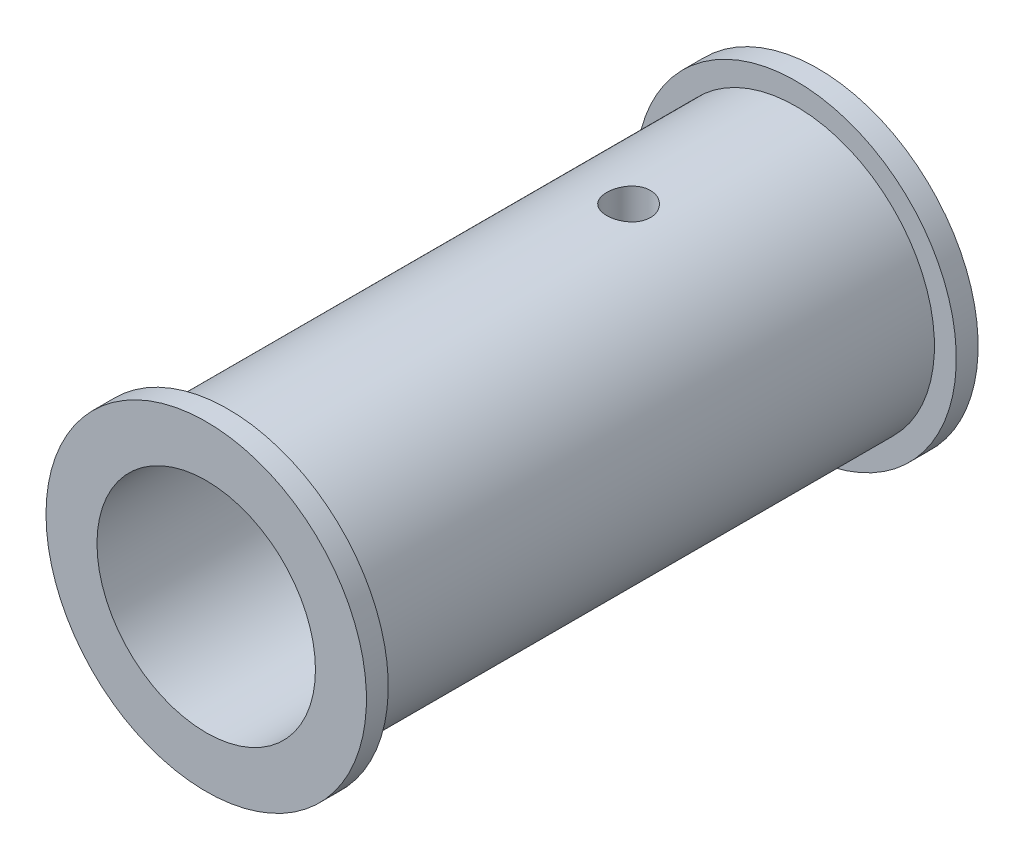
SolidWorks part; units mm, degrees
material "ABS"
ref_plane "Alzado" through (0, 0, 0) normal (0, 0, 1) x (1, 0, 0)
ref_plane "Planta" through (0, 0, 0) normal (0, 1, 0) x (1, 0, 0)
ref_plane "Vista lateral" through (0, 0, 0) normal (1, 0, 0) x (0, 0, -1)
sketch "Croquis1" plane through (0, 0, 0) normal (1, 0, 0) x (0, 0, -1)
  line L0 (0, 0) -> (-50000, 0) construction
  line L1 (-24, 7.5) -> (-24, 11)
  line L2 (-24, 7.5) -> (0, 7.5)
  line L3 (0, 7.5) -> (0, 0)
  line L4 (-24, 11) -> (-22.5, 11)
  line L5 (-22.5, 11) -> (-22.5, 9.5)
  line L6 (18, 8) -> (10, 8)
  line L7 (10, 8) -> (10, 0)
  line L8 (0, 0) -> (10, 0)
  line L9 (-22.5, 9.5) -> (16.5, 9.5)
  line L10 (16.5, 9.5) -> (16.5, 11)
  line L11 (16.5, 11) -> (18, 11)
  line L12 (18, 11) -> (18, 8)
  dimension "D1" = 16
  dimension "D2" = 1.5
  dimension "D3" = 1.5
  dimension "D4" = 1.5
  dimension "D5" = 42
  dimension "D6" = 8
  dimension "D7" = 2
  dimension "D8" = 10
revolve "Revolución1" add sketch "Croquis1" angle 360 about L0
sketch "Croquis2" plane through (0, 0, -10) normal (0, 0, -1) x (-1, 0, 0)
  line L0 (-1.118, 1) -> (1.118, 1)
  arc A0 (-1.118, 1) -> (1.118, 1) centre (0, 0) ccw
  dimension "D1" = 1.5
  dimension "D2" = 1
extrude "Cortar-Extruir1" cut sketch "Croquis2" against normal through all
sketch "Croquis3" plane through (0, 0, -10) normal (0, 0, -1) x (-1, 0, 0)
  line L0 (1.118, 1) -> (-1.118, 1) construction
  line L1 (-2.8, 4.5) -> (2.8, 4.5)
  line L2 (-2.8, 4.5) -> (-2.8, 2)
  line L3 (-2.8, 2) -> (2.8, 2)
  line L4 (2.8, 4.5) -> (2.8, 2)
  line L5 (-2.8, 4.5) -> (2.8, 2) construction
  line L6 (-2.8, 2) -> (2.8, 4.5) construction
  point P0 (0, 3.25)
  dimension "D1" = 2.5
  dimension "D2" = 5.6
  dimension "D3" = 1
extrude "Cortar-Extruir2" cut sketch "Croquis3" against normal blind 8
sketch "Croquis4" plane through (0, 0, 0) normal (0, 1, 0) x (1, 0, 0)
  line L0 (-1.5, 0) -> (1.5, 0) construction
  circle A0 centre (0, 5) radius 1.5
  dimension "D2" = 3
  dimension "D1" = 5
extrude "Cortar-Extruir3" cut sketch "Croquis4" along normal through all
